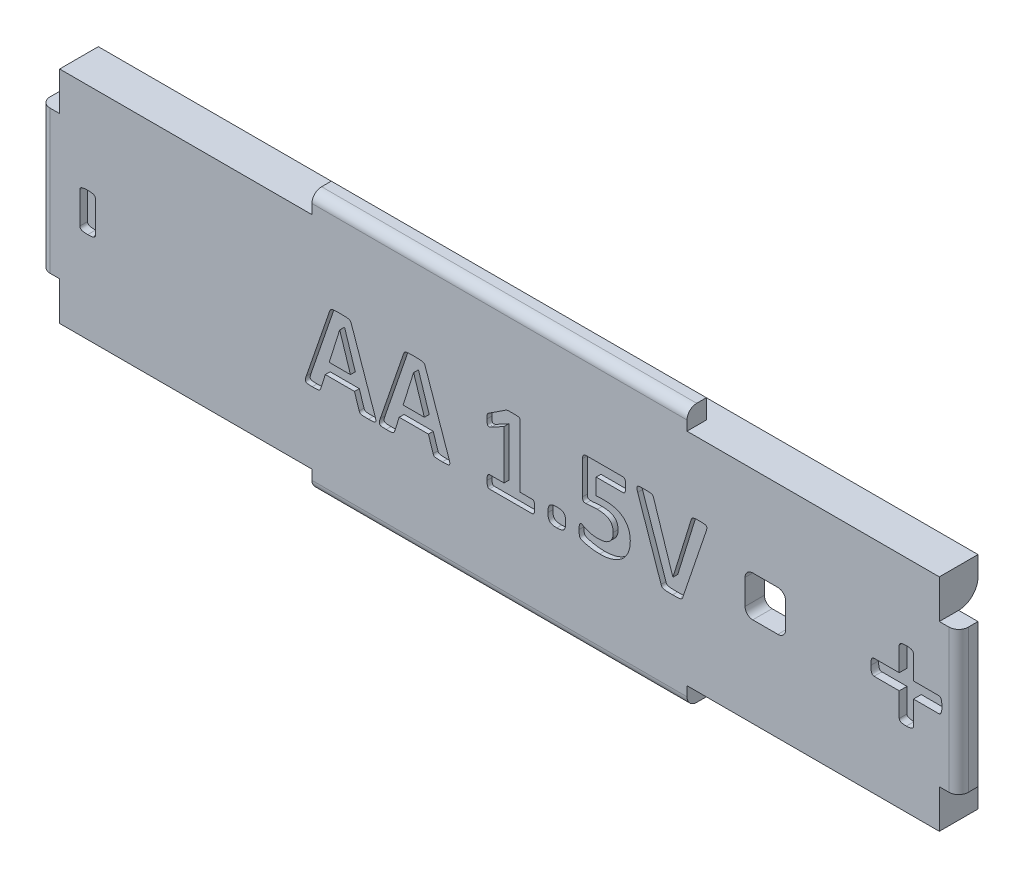
SolidWorks part; units mm, degrees
ref_plane "Front" through (0, 0, 0) normal (0, 0, 1) x (1, 0, 0)
ref_plane "Top" through (0, 0, 0) normal (0, 1, 0) x (1, 0, 0)
ref_plane "Right" through (0, 0, 0) normal (1, 0, 0) x (0, 0, -1)
sketch "Sketch1" plane through (0, 0, 0) normal (0, 0, 1) x (1, 0, 0)
  line L0 (-23.75, 0) -> (23.75, 0) construction
  line L1 (-22.75, -5.7) -> (-9.7, -5.7)
  line L2 (-22.75, -5.7) -> (-22.75, -3.7)
  line L3 (-22.75, 5.7) -> (-9.7, 5.7)
  line L4 (22.75, -5.7) -> (22.75, -3.7)
  line L5 (-22.75, -5.7) -> (22.75, 5.7) construction
  line L6 (-22.75, 5.7) -> (22.75, -5.7) construction
  line L8 (-9.7, 5.7) -> (-9.7, 6.7)
  line L9 (-9.7, 6.7) -> (9.7, 6.7)
  line L10 (9.7, 5.7) -> (9.7, 6.7)
  line L11 (-9.7, -6.7) -> (9.7, -6.7)
  line L12 (9.7, -5.7) -> (9.7, -6.7)
  line L14 (-9.7, -5.7) -> (-9.7, -6.7)
  line L15 (9.7, 5.7) -> (22.75, 5.7)
  line L16 (9.7, -5.7) -> (22.75, -5.7)
  line L17 (0, 6.7) -> (0, -6.7) construction
  line L18 (-23.75, 3.7) -> (-22.75, 3.7)
  line L19 (-23.75, 3.7) -> (-23.75, -3.7)
  line L20 (-23.75, -3.7) -> (-22.75, -3.7)
  line L22 (23.75, -3.7) -> (22.75, -3.7)
  line L23 (23.75, 3.7) -> (22.75, 3.7)
  line L24 (23.75, 3.7) -> (23.75, -3.7)
  line L25 (-22.75, 3.7) -> (-22.75, 5.7)
  line L26 (22.75, 3.7) -> (22.75, 5.7)
  point P0 (0, 0)
  point P10 (0, 6.7)
  dimension "D1" = 11.4
  dimension "D2" = 45.5
  dimension "D3" = 19.4
  dimension "D4" = 1
  dimension "D5" = 7.4
  dimension "D6" = 1
extrude "Boss-Extrude1" add sketch "Sketch1" along normal blind 1
fillet "Fillet1" radius 0.5 4 edges at (0, 6.7, 1) (23.75, 0, 1) (-23.75, 0, 1) (0, -6.7, 1)
sketch "Sketch2" plane through (0, 0, 1) normal (0, 0, 1) x (1, 0, 0)
  line L0 (-23.25, 0) -> (23.25, 0) construction
  line L1 (-23.25, 3.7) -> (-23.25, -3.7) construction
  line L2 (23.25, -3.7) -> (23.25, 3.7) construction
  line L3 (-23.25, -2) -> (23.25, -2) construction
  text T0 "<b>AA 1.5V</b>" font "Calibri" height 4
  dimension "D1" = 2
extrude "Cut-Extrude1" cut sketch "Sketch2" against normal blind 0.25
sketch "Sketch4" plane through (0, 0, 0) normal (0, 0, -1) x (-1, 0, 0)
  line L0 (-13.75, -1.05) -> (-13.75, 1.05) construction
  line L1 (-12.7, -1.05) -> (-14.8, -1.05)
  line L2 (-12.7, -1.05) -> (-12.7, 1.05)
  line L3 (-12.7, 1.05) -> (-14.8, 1.05)
  line L4 (-14.8, -1.05) -> (-14.8, 1.05)
  line L5 (-23.75, -3.7) -> (-23.75, 3.7) construction
  point P6 (-13.75, 0)
  point P9 (-23.75, 0)
  dimension "D1" = 10
  dimension "D2" = 2.1
  dimension "D3" = 2.1
extrude "Cut-Extrude3" cut sketch "Sketch4" against normal through all
fillet "Fillet2" radius 0.4 4 edges at (12.7, -1.05, 0.5) (14.8, -1.05, 0.5) (12.7, 1.05, 0.5) (14.8, 1.05, 0.5)
sketch "Sketch6" plane through (0, 0, 1) normal (0, 0, 1) x (1, 0, 0)
  text T0 "<b>+</b>" font "Calibri" height 5
  text T1 "<b>-</b>" font "Calibri" height 5
extrude "Cut-Extrude4" cut sketch "Sketch6" against normal blind 0.4
sketch "Sketch7" plane through (0, 0, 0) normal (0, 0, -1) x (-1, 0, 0)
  line L0 (-22.75, 3.7) -> (-22.75, 5.7) construction
  line L1 (-22.75, 5.7) -> (22.75, 5.7) construction
  line L2 (22.75, 5.7) -> (22.75, 3.7) construction
  line L3 (9.7, 5.7) -> (22.75, 5.7) construction
  line L4 (22.75, 5.7) -> (22.75, 3.7) construction
  line L5 (-22.75, 3.7) -> (-22.75, 5.7)
  line L6 (-22.75, 5.7) -> (22.75, 5.7)
  line L7 (22.75, 5.7) -> (22.75, 3.7)
  line L9 (-21.75, 3.7) -> (-21.75, 4.7)
  line L10 (-21.75, 4.7) -> (21.75, 4.7)
  line L11 (21.75, 4.7) -> (21.75, 3.7)
  line L12 (-22.75, 3.7) -> (-21.75, 3.7)
  line L13 (21.75, 3.7) -> (22.75, 3.7)
  line L14 (-23.75, 0) -> (23.75, 0) construction
  line L15 (-23.75, -3.7) -> (-23.75, 3.7) construction
  line L16 (23.75, 3.7) -> (23.75, -3.7) construction
  line L17 (21.75, -4.7) -> (21.75, -3.7)
  line L18 (-21.75, -4.7) -> (21.75, -4.7)
  line L19 (-21.75, -3.7) -> (-21.75, -4.7)
  line L20 (-22.75, -3.7) -> (-21.75, -3.7)
  line L21 (-22.75, -3.7) -> (-22.75, -5.7)
  line L22 (-22.75, -5.7) -> (22.75, -5.7)
  line L23 (22.75, -5.7) -> (22.75, -3.7)
  line L24 (21.75, -3.7) -> (22.75, -3.7)
  dimension "D2" = 1
extrude "Boss-Extrude2" add sketch "Sketch7" along normal blind 1
fillet "Fillet3" radius 1 2 edges at (22.25, -3.7, -1) (22.25, 3.7, -1)
